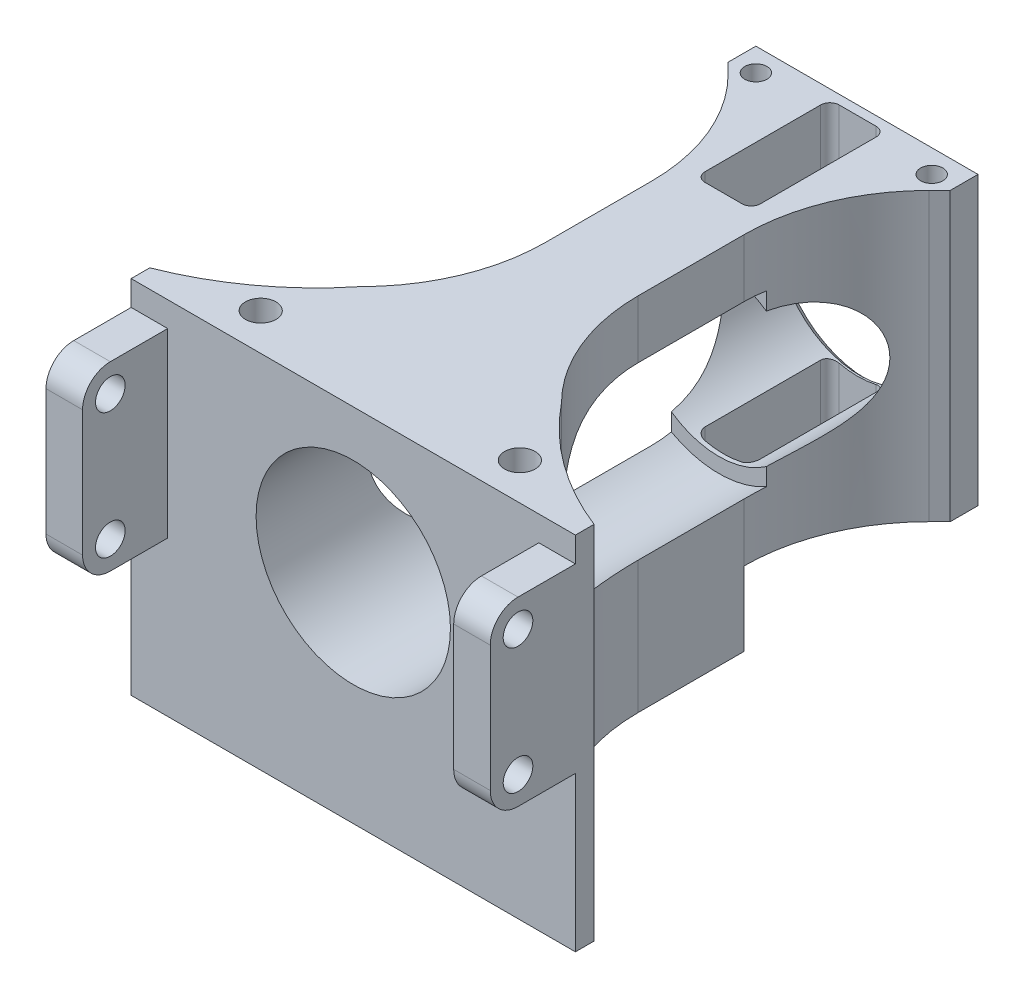
SolidWorks part; units mm, degrees
material "6061 合金"
ref_plane "前视基准面" through (0, 0, 0) normal (0, 0, 1) x (1, 0, 0)
ref_plane "上视基准面" through (0, 0, 0) normal (0, 1, 0) x (1, 0, 0)
ref_plane "右视基准面" through (0, 0, 0) normal (1, 0, 0) x (0, 0, -1)
sketch "草图1" plane through (0, 0, 0) normal (0, 0, 1) x (1, 0, 0)
  line L1 (-24, -15.5) -> (24, -15.5)
  line L2 (-24, -15.5) -> (-24, 15.5)
  line L3 (-24, 15.5) -> (24, 15.5)
  line L4 (24, -15.5) -> (24, 15.5)
  line L5 (-24, -15.5) -> (24, 15.5) construction
  line L6 (-24, 15.5) -> (24, -15.5) construction
  circle A0 centre (0, 0) radius 8.9
  point P0 (0, 0)
  dimension "D3" = 17.8
  dimension "D1" = 48
  dimension "D2" = 31
extrude "凸台-拉伸1" add sketch "草图1" along normal blind 65
sketch "草图2" plane through (0, 0, 65) normal (0, 0, 1) x (1, 0, 0)
  circle A0 centre (0, 0) radius 10.5
  dimension "D1" = 21
extrude "切除-拉伸1" cut sketch "草图2" against normal offset from surface (49 mm away) 16 up to face at (0, 0, 0)
sketch "草图4" plane through (0, 15.5, 0) normal (0, 1, 0) x (1, 0, 0)
  line L0 (-24, 9) -> (-10.8579, -4.1421)
  line L1 (-24, -65) -> (-24, 0) construction
  line L2 (-5, -18.2843) -> (-5, -29.7157)
  line L3 (-10.8579, -43.8579) -> (-24, -57) construction
  line L4 (-24, -57) -> (-24, 9) construction
  line L5 (0, 0) -> (0, -65) construction
  line L6 (24, -65) -> (-24, -65) construction
  line L7 (-24, -65) -> (-24, -62) construction
  line L8 (-24, -62) -> (-21, -62) construction
  line L9 (24, 0) -> (-24, 0) construction
  line L10 (10.8579, -43.8579) -> (24, -57) construction
  line L11 (5, -18.2843) -> (5, -29.7157)
  line L12 (24, 9) -> (10.8579, -4.1421)
  line L13 (24, -57) -> (24, 9) construction
  line L14 (35.5, -24) -> (-35.5, -24) construction
  line L15 (9.5, -2.5) -> (-9.5, -2.5) construction
  line L16 (24, -53.4842) -> (24, 9)
  line L17 (-24, -53.4842) -> (-24, 9)
  arc A2 (5, -18.2843) -> (10.8579, -4.1421) centre (25, -18.2843) cw
  arc A3 (10.8579, -43.8579) -> (5, -29.7157) centre (25, -29.7157) cw
  arc A4 (-5, -29.7157) -> (-10.8579, -43.8579) centre (-25, -29.7157) cw
  arc A5 (-10.8579, -4.1421) -> (-5, -18.2843) centre (-25, -18.2843) cw
  circle A6 centre (-35.5, -24) radius 30 construction
  circle A7 centre (35.5, -24) radius 30 construction
  circle A8 centre (9.5, -2.5) radius 1.2 construction
  circle A9 centre (-9.5, -2.5) radius 1.2 construction
  arc A10 (-10.8579, -43.8579) -> (-24, -53.4842) centre (-35.5, -24) cw
  arc A11 (10.8579, -43.8579) -> (24, -53.4842) centre (35.5, -24) ccw
  point P12 (-5, -24)
  point P26 (5, -10)
  point P29 (5, -38)
  point P32 (-5, -38)
  point P35 (-5, -10)
  point P36 (0, -24)
  point P41 (0, -2.5)
  dimension "D3" = 24
  dimension "D7" = 20
  dimension "D4" = 60
  dimension "D11" = 2.4
  dimension "D1" = 3
  dimension "D2" = 3
  dimension "D5" = 10
  dimension "D6" = 10
  dimension "D8" = 71
  dimension "D9" = 2.5
  dimension "D10" = 19
  dimension "D12" = 135
extrude "切除-拉伸3" cut sketch "草图4" against normal through all
sketch "草图6" plane through (0, 15.5, 0) normal (0, 1, 0) x (1, 0, 0)
  line L0 (0, 0) -> (0, -1) construction
  line L1 (-2, -1) -> (2, -1)
  line L2 (-3, -2) -> (-3, -14.5)
  line L3 (-2, -15.5) -> (2, -15.5)
  line L4 (3, -2) -> (3, -14.5)
  arc A0 (-3, -14.5) -> (-2, -15.5) centre (-2, -14.5) ccw
  arc A1 (2, -15.5) -> (3, -14.5) centre (2, -14.5) ccw
  arc A2 (2, -1) -> (3, -2) centre (2, -2) cw
  arc A3 (-2, -1) -> (-3, -2) centre (-2, -2) ccw
  point P9 (-3, -15.5)
  point P14 (3, -1)
  point P17 (-3, -1)
  dimension "D4" = 1
  dimension "D1" = 1
  dimension "D2" = 14.5
  dimension "D3" = 6
extrude "切除-拉伸5" cut sketch "草图6" along normal through all from surface starting at face at (0, -15.5, 30.7635)
sketch "草图9" plane through (0, 15.5, 0) normal (0, 1, 0) x (1, 0, 0)
  line L0 (9.5, -2.5) -> (-9.5, -2.5) construction
  line L1 (0, -2.5) -> (0, 0) construction
  circle A0 centre (9.5, -2.5) radius 1.2
  circle A1 centre (-9.5, -2.5) radius 1.2
  dimension "D3" = 2.4
  dimension "D1" = 2.5
  dimension "D2" = 19
extrude "切除-拉伸6" cut sketch "草图9" against normal blind 7
cosmetic thread "装饰螺纹线1" parameters "D2"=3
cosmetic thread "装饰螺纹线2" parameters "D2"=3
extrude "切除-拉伸7" cut sketch "草图9<2>" along normal blind 7 from surface starting at face at (0, -15.5, 8.25)
sketch "草图9<2>" plane through (0, 15.5, 0) normal (0, 1, 0) x (1, 0, 0) same geometry as "草图9"
cosmetic thread "装饰螺纹线3" parameters "D2"=3
cosmetic thread "装饰螺纹线4" parameters "D2"=3
sketch "草图12" plane through (0, -15.5, 0) normal (0, -1, 0) x (1, 0, 0)
  line L0 (-5, 18.2843) -> (5, 18.2843)
  line L12 (-15, 0) -> (15, 0)
  line L14 (15, 0) -> (10.8579, 4.1421)
  line L15 (5, 18.2843) -> (5, 29.7157)
  line L17 (24, 53.4842) -> (24, 65)
  line L18 (24, 65) -> (-24, 65)
  line L19 (-24, 65) -> (-24, 53.4842)
  line L21 (-5, 29.7157) -> (-5, 18.2843)
  line L22 (-10.8579, 4.1421) -> (-15, 0)
  line L24 (-15, 0) -> (15, 0) construction
  line L26 (15, 0) -> (10.8579, 4.1421) construction
  line L27 (5, 18.2843) -> (5, 29.7157)
  line L29 (24, 53.4842) -> (24, 65)
  line L30 (24, 65) -> (-24, 65)
  line L31 (-24, 65) -> (-24, 53.4842)
  line L33 (-5, 29.7157) -> (-5, 18.2843)
  line L34 (-10.8579, 4.1421) -> (-15, 0) construction
  arc A4 (5, 18.2843) -> (10.8579, 4.1421) centre (25, 18.2843) ccw
  arc A5 (10.8579, 43.8579) -> (5, 29.7157) centre (25, 29.7157) ccw
  arc A6 (-5, 29.7157) -> (-10.8579, 43.8579) centre (-25, 29.7157) ccw
  arc A7 (-10.8579, 4.1421) -> (-5, 18.2843) centre (-25, 18.2843) ccw
  arc A8 (5, 18.2843) -> (10.8579, 4.1421) centre (25, 18.2843) ccw construction
  arc A9 (10.8579, 43.8579) -> (5, 29.7157) centre (25, 29.7157) ccw
  arc A10 (-5, 29.7157) -> (-10.8579, 43.8579) centre (-25, 29.7157) ccw
  arc A11 (-10.8579, 4.1421) -> (-5, 18.2843) centre (-25, 18.2843) ccw construction
  arc A14 (24, 53.4842) -> (10.8579, 43.8579) centre (35.5, 24) ccw
  arc A15 (24, 53.4842) -> (10.8579, 43.8579) centre (35.5, 24) ccw
  arc A16 (-10.8579, 43.8579) -> (-24, 53.4842) centre (-35.5, 24) ccw
  arc A17 (-10.8579, 43.8579) -> (-24, 53.4842) centre (-35.5, 24) ccw
  dimension "D1" = 0
extrude "凸台-拉伸4" add sketch "草图12" along normal blind 8
sketch "草图11" plane through (0, 15.5, 0) normal (0, 1, 0) x (1, 0, 0)
  line L0 (14, -51.5) -> (-14, -51.5) construction
  line L1 (0, -51.5) -> (0, 0) construction
  circle A0 centre (14, -51.5) radius 1.65
  circle A1 centre (-14, -51.5) radius 1.65
  dimension "D3" = 3.3
  dimension "D1" = 51.5
  dimension "D2" = 28
extrude "切除-拉伸9" cut sketch "草图11" against normal through all
cosmetic thread "装饰螺纹线5" parameters "D2"=4
cosmetic thread "装饰螺纹线6" parameters "D2"=4
cosmetic thread "装饰螺纹线7" parameters "D2"=4
cosmetic thread "装饰螺纹线8" parameters "D2"=4
sketch "草图14" plane through (0, -23.5, 0) normal (0, -1, 0) x (1, 0, 0)
  line L0 (-5, 24) -> (5, 24) construction
  line L1 (-5, 29.7157) -> (-5, 18.2843) construction
  line L2 (5, 18.2843) -> (5, 29.7157) construction
  circle A0 centre (0, 24) radius 1.65
  dimension "D1" = 3.3
extrude "切除-拉伸10" cut sketch "草图14" against normal blind 11
cosmetic thread "装饰螺纹线9" parameters "D2"=4
sketch "草图15" plane through (0, 15.5, 0) normal (0, 1, 0) x (1, 0, 0)
  line L0 (24, -65) -> (-24, -65) construction
  line L1 (20.05, -65) -> (-20.05, -65)
  line L2 (20.05, -65) -> (20.05, -55.5)
  line L3 (20.05, -55.5) -> (-20.05, -55.5)
  line L4 (-20.05, -65) -> (-20.05, -55.5)
  line L5 (0, 0) -> (0, -55.5) construction
  circle A0 centre (-14, -51.5) radius 1.65 construction
  dimension "D1" = 40.1
  dimension "D2" = 4
extrude "切除-拉伸11" cut sketch "草图15" against normal through all
sketch "草图17" plane through (24, 0, 0) normal (1, 0, 0) x (0, 0, -1)
  line L0 (-53.4842, -23.5) -> (-65, -23.5) construction
  line L1 (-65, 15.5) -> (-53.4842, 15.5) construction
  line L2 (-61.7, 9.8) -> (-61.7, -3.8) construction
  line L3 (-61.7, 3) -> (-55.5, 3) construction
  line L4 (-55.5, -23.5) -> (-55.5, -6.8)
  line L5 (-55.5, -6.8) -> (-61.7, -6.8)
  line L6 (-64.7, -3.8) -> (-64.7, 9.8)
  line L9 (-64.7, 15.5) -> (-94.5, 15.5)
  line L10 (-94.5, 15.5) -> (-94.5, -23.5)
  line L11 (-94.5, -23.5) -> (-55.5, -23.5)
  line L12 (-55.5, -23.5) -> (-55.5, 15.5) construction
  line L13 (-61.7, 12.8) -> (-55.5, 12.8)
  line L14 (-55.5, 12.8) -> (-55.5, 15.5)
  line L15 (-55.5, 15.5) -> (-64.7, 15.5)
  circle A0 centre (-61.7, 9.8) radius 1.6
  circle A1 centre (-61.7, -3.8) radius 1.6
  arc A3 (-61.7, -6.8) -> (-64.7, -3.8) centre (-61.7, -3.8) cw
  arc A4 (-61.7, 12.8) -> (-64.7, 9.8) centre (-61.7, 9.8) ccw
  dimension "D3" = 3.2
  dimension "D4" = 3
  dimension "D1" = 13.6
  dimension "D2" = 6.2
  dimension "D6" = 12.5
extrude "切除-拉伸13" cut sketch "草图17" against normal through all
sketch "草图19" plane through (0, -15.5, 0) normal (0, -1, 0) x (1, 0, 0)
  line L0 (-10.8579, 4.1421) -> (-15, 0) construction
  line L1 (-15, 0) -> (-12, 0)
  line L2 (-15, 0) -> (-15, 3)
  line L3 (-15, 3) -> (-12, 3)
  line L4 (-12, 0) -> (-12, 3)
  line L5 (15, 0) -> (10.8579, 4.1421) construction
  line L6 (15, 0) -> (12, 0)
  line L7 (15, 0) -> (15, 3)
  line L8 (15, 3) -> (12, 3)
  line L9 (12, 0) -> (12, 3)
  dimension "D1" = 3
extrude "切除-拉伸14" cut sketch "草图19" against normal through all
chamfer "倒角1" distance 0.8 angle 45 1 edges at (8.9, 0, 0)
